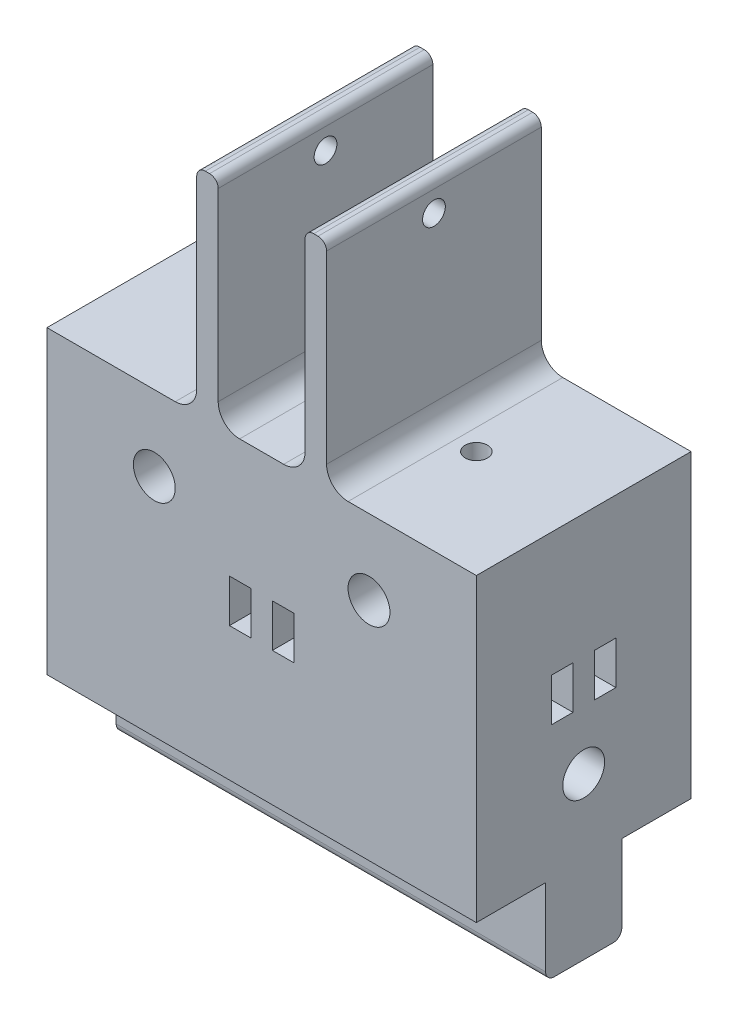
SolidWorks part; units mm, degrees
ref_plane "Front Plane" through (0, 0, 0) normal (0, 0, 1) x (1, 0, 0)
ref_plane "Top Plane" through (0, 0, 0) normal (0, 1, 0) x (1, 0, 0)
ref_plane "Right Plane" through (0, 0, 0) normal (1, 0, 0) x (0, 0, -1)
sketch "Sketch1" plane through (0, 0, 0) normal (0, 0, 1) x (1, 0, 0)
  line L1 (-50, -35) -> (50, -35)
  line L2 (-50, -35) -> (-50, 35)
  line L3 (-50, 35) -> (50, 35)
  line L4 (50, -35) -> (50, 35)
  line L5 (-50, -35) -> (50, 35) construction
  line L6 (-50, 35) -> (50, -35) construction
  point P0 (0, 0)
  dimension "D1" = 70
  dimension "D2" = 100
extrude "Boss-Extrude1" add sketch "Sketch1" along normal mid plane 50
sketch "Sketch2" plane through (0, 0, 25) normal (0, 0, 1) x (1, 0, 0)
  line L0 (0, 0) -> (50, 35) construction
  line L1 (0, 0) -> (-50, 35) construction
  circle A0 centre (25, 17.5) radius 4.875
  circle A1 centre (-25, 17.5) radius 4.875
  dimension "D1" = 9.75
extrude "Cut-Extrude1" cut sketch "Sketch2" against normal through all both and the other way through all
sketch "Sketch3" plane through (-50, 0, 0) normal (-1, 0, 0) x (0, 0, 1)
  line L0 (0, 0) -> (0, -35) construction
  line L1 (25, -35) -> (-25, -35) construction
  circle A0 centre (0, -17.5) radius 4.875
  dimension "D1" = 9.75
extrude "Cut-Extrude2" cut sketch "Sketch3" against normal through all both
sketch "Sketch4" plane through (0, 35, 0) normal (0, 1, 0) x (1, 0, 0)
  line L0 (-50, 0) -> (0, 0) construction
  line L1 (-50, -25) -> (-50, 25) construction
  line L3 (0, 0) -> (50, 0) construction
  line L4 (50, -25) -> (50, 25) construction
  circle A0 centre (-25, 0) radius 2.6
  circle A1 centre (25, 0) radius 2.6
  point P5 (-25, 0)
  dimension "D1" = 5.2
extrude "Cut-Extrude4" cut sketch "Sketch4" against normal blind 20
sketch "Sketch5" plane through (0, -35, 0) normal (0, -1, 0) x (1, 0, 0)
  line L0 (50, 25) -> (50, -25) construction
  line L1 (-50, -8.875) -> (50, -8.875)
  line L2 (-50, -8.875) -> (-50, 8.875)
  line L3 (-50, 8.875) -> (50, 8.875)
  line L4 (50, -8.875) -> (50, 8.875)
  line L5 (-50, -8.875) -> (50, 8.875) construction
  line L6 (-50, 8.875) -> (50, -8.875) construction
  point P0 (0, 0)
  dimension "D1" = 17.75
extrude "Boss-Extrude2" add sketch "Sketch5" along normal blind 20
fillet "Fillet1" radius 2 2 edges at (0, -55, -8.875) (0, -55, 8.875)
sketch "Sketch6" plane through (0, 35, 0) normal (0, 1, 0) x (1, 0, 0)
  line L0 (50, 25) -> (-50, 25) construction
  line L1 (-15.125, 25) -> (-10.125, 25)
  line L2 (-15.125, 25) -> (-15.125, -25)
  line L3 (-15.125, -25) -> (-10.125, -25)
  line L4 (-10.125, 25) -> (-10.125, -25)
  line L5 (50, -25) -> (-50, -25) construction
  line L6 (-10.125, 0) -> (10.125, 0) construction
  line L7 (15.125, 25) -> (10.125, 25)
  line L8 (15.125, 25) -> (15.125, -25)
  line L9 (15.125, -25) -> (10.125, -25)
  line L10 (10.125, 25) -> (10.125, -25)
  point P16 (0, 0)
  dimension "D1" = 20.25
  dimension "D2" = 5
extrude "Boss-Extrude3" add sketch "Sketch6" along normal blind 50
sketch "Sketch7" plane through (15.125, 0, 0) normal (1, 0, 0) x (0, 0, -1)
  line L0 (0, 85) -> (0, 78.15) construction
  line L1 (-25, 85) -> (25, 85) construction
  circle A0 centre (0, 78.15) radius 2.65
  dimension "D2" = 5.3
  dimension "D1" = 6.85
extrude "Cut-Extrude5" cut sketch "Sketch7" against normal through all both
fillet "Fillet2" radius 5 4 edges at (-15.125, 35, 0) (-10.125, 35, 0) (10.125, 35, 0) (15.125, 35, 0)
fillet "Fillet3" radius 2 4 edges at (15.125, 85, 0) (10.125, 85, 0) (-10.125, 85, 0) (-15.125, 85, 0)
sketch "Sketch8" plane through (-50, 0, 0) normal (-1, 0, 0) x (0, 0, 1)
  line L0 (0, 35) -> (0, 6.15) construction
  line L1 (-2.5, -3.85) -> (-2.5, 6.15)
  line L2 (-7.5, 6.15) -> (7.5, 6.15)
  line L3 (-7.5, 6.15) -> (-7.5, -3.85)
  line L4 (-7.5, -3.85) -> (7.5, -3.85)
  line L5 (7.5, 6.15) -> (7.5, -3.85)
  line L6 (2.5, -3.85) -> (2.5, 6.15)
  line L7 (25, 35) -> (-25, 35) construction
  point P6 (0, 6.15)
  point P11 (0, 0)
  point P14 (0, 35)
  dimension "D1" = 28.85
  dimension "D2" = 15
  dimension "D3" = 10
  dimension "D4" = 5
  dimension "D5" = 5
extrude "Cut-Extrude6" cut sketch "Sketch8" against normal through all both contours L6 L4 L5 L2 | L3 L4 L1 L2 region at (-50, 1.15, -5) region at (-50, 1.15, 5)
sketch "Sketch9" plane through (0, 0, 25) normal (0, 0, 1) x (1, 0, 0)
  line L0 (0, -35) -> (0, 6.15)
  line L1 (-7.5, 6.15) -> (7.5, 6.15)
  line L2 (-7.5, 6.15) -> (-7.5, -3.85)
  line L3 (-7.5, -3.85) -> (7.5, -3.85)
  line L4 (7.5, 6.15) -> (7.5, -3.85)
  line L5 (-2.5, 6.15) -> (2.5, 6.15)
  line L6 (-2.5, 6.15) -> (-2.5, -3.85)
  line L7 (-2.5, -3.85) -> (2.5, -3.85)
  line L8 (2.5, 6.15) -> (2.5, -3.85)
  line L9 (-50, -35) -> (50, -35) construction
  line L10 (-20.125, 35) -> (-50, 35) construction
  point P6 (0, 6.15)
  point P11 (0, 0)
  point P14 (0, -35)
  dimension "D1" = 15
  dimension "D2" = 10
  dimension "D3" = 5
  dimension "D4" = 5
  dimension "D5" = 28.85
extrude "Cut-Extrude7" cut sketch "Sketch9" against normal through all both contours L1 L8 L3 L4 | L6 L1 L2 L3 region at (-5, 1.15, 25) region at (5, 1.15, 25)
fillet "Fillet4" radius 10 4 edges at (7.5, 1.15, 7.5) (7.5, 1.15, -7.5) (-7.5, 1.15, -7.5) (-7.5, 1.15, 7.5)
